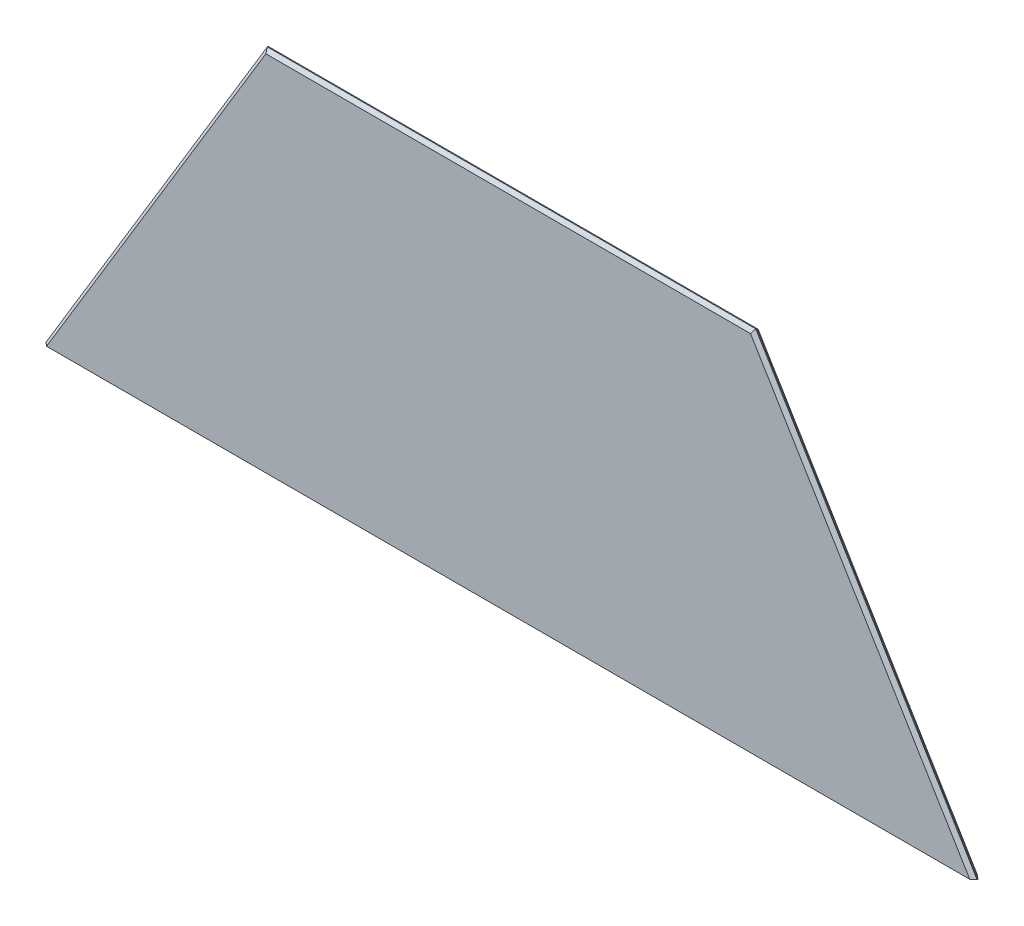
SolidWorks part; units mm, degrees
material "Printed Circuit Board"
ref_plane "Front Plane" through (0, 0, 0) normal (0, 0, 1) x (1, 0, 0)
ref_plane "Top Plane" through (0, 0, 0) normal (0, 1, 0) x (1, 0, 0)
ref_plane "Right Plane" through (0, 0, 0) normal (1, 0, 0) x (0, 0, -1)
sketch "Sketch1" plane through (0, 0, 0) normal (0, 0, 1) x (1, 0, 0)
  line L0 (0, 0) -> (193.675, 0)
  line L1 (193.675, 0) -> (101.6, 152.4)
  line L2 (101.6, 152.4) -> (0, 152.4)
  line L3 (0, 152.4) -> (-101.6, 152.4)
  line L4 (-101.6, 152.4) -> (-193.675, 0)
  line L5 (-193.675, 0) -> (0, 0)
  line L6 (0, 0) -> (0, 152.4) construction
  dimension "D1" = 152.4
  dimension "D2" = 387.35
  dimension "D3" = 203.2
extrude "Extrude1" add sketch "Sketch1" along normal mid plane 3.175
chamfer "Chamfer1" distance 1.397 angle 45 6 edges at (147.6375, 76.2, -1.5875) (0, 152.4, -1.5875) (-147.6375, 76.2, -1.5875) (147.6375, 76.2, 1.5875) (0, 152.4, 1.5875) (-147.6375, 76.2, 1.5875)
